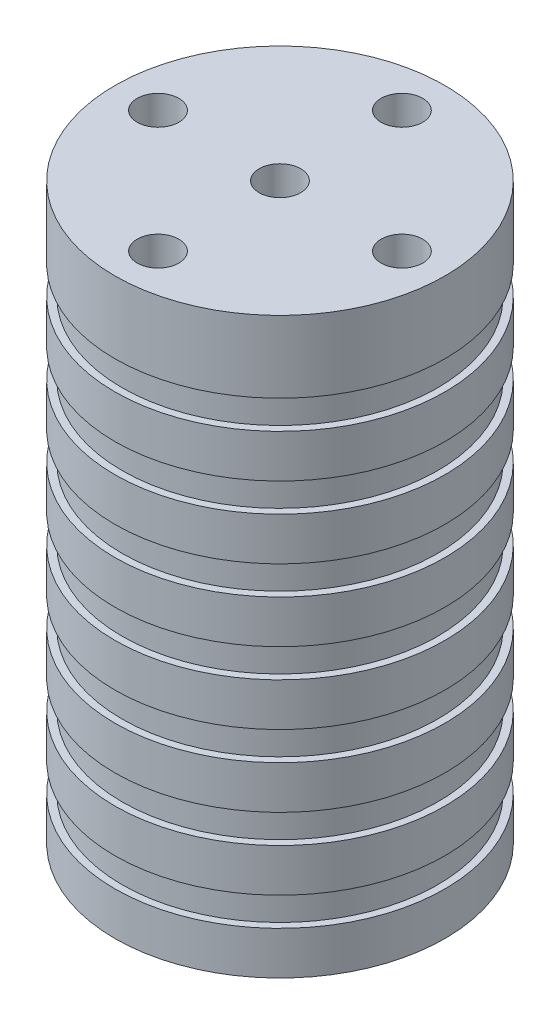
SolidWorks part; units mm, degrees
ref_plane "Front Plane" through (0, 0, 0) normal (0, 0, 1) x (1, 0, 0)
ref_plane "Top Plane" through (0, 0, 0) normal (0, 1, 0) x (1, 0, 0)
ref_plane "Right Plane" through (0, 0, 0) normal (1, 0, 0) x (0, 0, -1)
sketch "Sketch2" plane through (0, 0, 0) normal (0, 0, 1) x (1, 0, 0)
  line L0 (-11.5, 0) -> (11.5, 0)
  line L1 (11.5, 0) -> (11.5, -40)
  line L2 (11.5, -40) -> (5.5, -40)
  line L3 (5.5, -40) -> (5.5, -7)
  line L4 (0, 0) -> (0, -7)
  line L5 (-5.5, -40) -> (-5.5, -7)
  line L6 (-11.5, -40) -> (-5.5, -40)
  line L7 (-11.5, 0) -> (-11.5, -40)
  line L8 (-5.5, -7) -> (5.5, -7)
  point P4 (0, 0)
  dimension "D1" = 23
  dimension "D2" = 7
  dimension "D3" = 6
  dimension "D4" = 40
revolve "Revolve1" add sketch "Sketch2" angle 360 about L4 region at (-7.7051, -17.719, 0)
sketch "Sketch3" plane through (0, 0, 0) normal (0, 0, 1) x (1, 0, 0)
  line L0 (-11.5, -40) -> (11.5, -40) construction
  line L1 (-11.5, -40) -> (11.5, -40)
  line L2 (11.5, -40) -> (11.5, -37)
  line L3 (11.5, -40) -> (11.5, 0) construction
  line L4 (11.5, -37) -> (11, -37)
  line L5 (11, -37) -> (11, -35)
  line L6 (11, -35) -> (11.5, -35)
  line L7 (11.5, -37) -> (11.5, -35)
  dimension "D1" = 2
  dimension "D2" = 0.5
  dimension "D3" = 3
revolve "Cut-Revolve1" cut sketch "Sketch3" angle 360 about L4
pattern_linear "LPattern1" count 7 spacing 5 along (0, 1, 0) of "Cut-Revolve1"
sketch "Sketch4" plane through (0, 0, 0) normal (0, 1, 0) x (1, 0, 0)
  line L0 (-11.5, 0) -> (-11.5, 8.5) construction
  line L1 (-10.25, 0) -> (-10.25, 5.2142) construction
  line L2 (-11.5, 0) -> (-5.5, 0) construction
  circle A0 centre (0, 0) radius 8.5 construction
  circle A1 centre (0, 8.5) radius 1.75 construction
  circle A2 centre (8.5, 0) radius 1.75 construction
  circle A3 centre (0, -8.5) radius 1.75 construction
  circle A4 centre (-8.5, 0) radius 1.75 construction
  circle A5 centre (0, 0) radius 11.5 construction
  circle A7 centre (0, 0) radius 5.5
  circle A8 centre (0, 0) radius 5.5 construction
  point P0 (8.5, 0)
  point P14 (0, 0)
  point P19 (-8.5, 0)
  point P23 (0, 8.5)
  point P25 (0, -8.5)
  dimension "D3" = 3.5
  dimension "D4" = 0
  dimension "D1" = 4
hole_wizard "M3.5x0.6 Tapped Hole1" positions "Sketch4" profile "Sketch5" tap size "M3.5x0.6" standard "ANSI Metric"
sketch "Sketch5" plane through (8.5, 0, 0) normal (1, 0, 0) x (0, 0, 1)
  line L0 (0, 0) -> (0, 10.8712)
  line L1 (0, 10.8712) -> (1.45, 10)
  line L2 (1.45, 10) -> (1.45, 0)
  line L5 (1.45, 0) -> (0, 0)
  line L10 (0, 10.8712) -> (-1.45, 10) construction
  line L11 (0, -6.35) -> (0, 107.95) construction
  dimension "Tap Drill Dia." = 2.9
  dimension "Tap Drill Depth" = 10
  dimension "Drill Angle" = 118
cosmetic thread "Hole Thread1" parameters "D1"=7, "D2"=3.5
cosmetic thread "Hole Thread2" parameters "D1"=7, "D2"=3.5
cosmetic thread "Hole Thread3" parameters "D1"=7, "D2"=3.5
cosmetic thread "Hole Thread4" parameters "D1"=7, "D2"=3.5
cosmetic thread "Hole Thread5" parameters "D1"=7, "D2"=3.5
